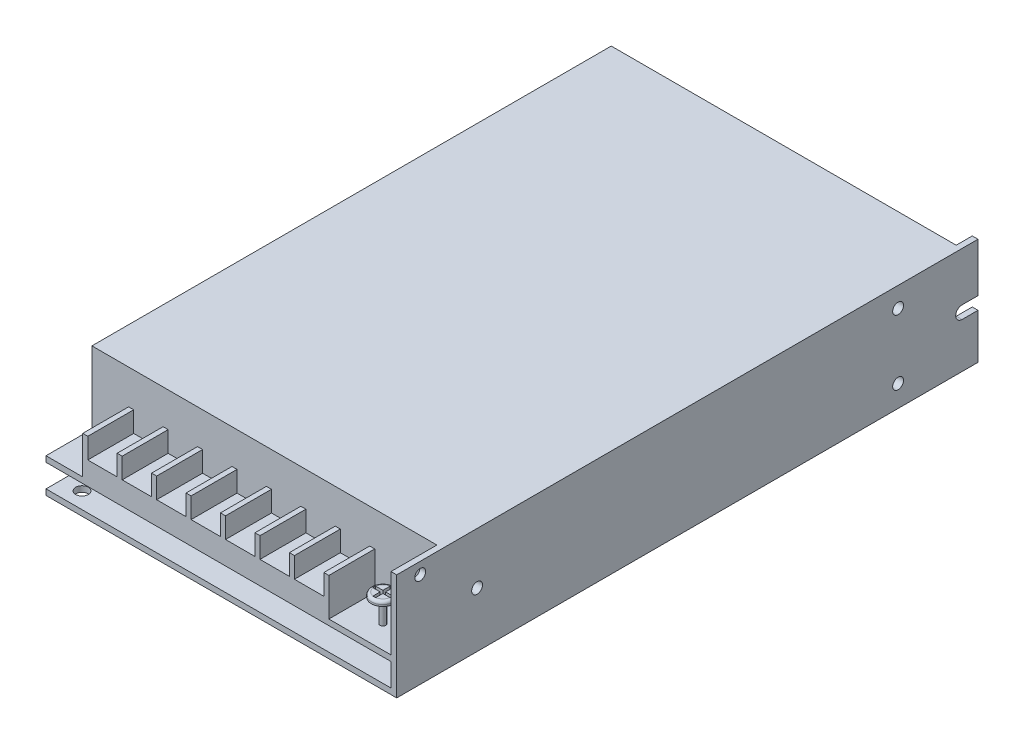
SolidWorks part; units mm, degrees
ref_plane "Front (1)" through (0, 0, 0) normal (0, 0, 1) x (1, 0, 0)
ref_plane "Top (2)" through (0, 0, 0) normal (0, 1, 0) x (1, 0, 0)
ref_plane "Right (3)" through (0, 0, 0) normal (1, 0, 0) x (0, 0, -1)
ref_axis "X-Axis" through (-80.9, 0, 0) along (1, 0, 0)
ref_axis "Y-Axis" through (0, -50, 0) along (0, 1, 0)
ref_axis "Z-Axis" through (0, 0, 50) along (0, 0, -1)
sketch "Sketch1" plane through (0, 0, 0) normal (0, 0, 1) x (1, 0, 0)
  line L1 (0, 0) -> (97, 0)
  line L2 (0, 0) -> (0, 29.492)
  line L3 (0, 29.492) -> (97, 29.492)
  line L4 (97, 0) -> (97, 29.492)
  dimension "D1" = 97
  dimension "D2" = 29.492
extrude "Boss-Extrude1" add sketch "Sketch1" against normal blind 160.778
sketch "Sketch2" plane through (0, 0, 0) normal (0, 0, 1) x (1, 0, 0)
  line L0 (95.4125, 29.492) -> (95.4125, 9.525)
  line L1 (97, 29.492) -> (0, 29.492) construction
  line L2 (95.4125, 9.525) -> (89.9973, 9.525)
  line L3 (59.182, 19.967) -> (59.182, 14.2875)
  line L4 (59.182, 14.2875) -> (67.31, 14.2875)
  line L5 (67.31, 14.2875) -> (67.31, 19.967)
  line L6 (67.31, 19.967) -> (68.707, 19.967)
  line L7 (89.9973, 9.525) -> (89.9973, 17.145)
  line L8 (89.9973, 17.145) -> (83.6472, 17.145)
  line L9 (83.6472, 17.145) -> (83.6472, 9.525)
  line L10 (83.6472, 9.525) -> (78.232, 9.525)
  line L11 (68.707, 19.967) -> (68.707, 14.2875)
  line L12 (59.182, 19.967) -> (57.785, 19.967)
  line L13 (57.785, 19.967) -> (57.785, 14.2875)
  line L14 (57.785, 14.2875) -> (49.657, 14.2875)
  line L15 (49.657, 14.2875) -> (49.657, 19.967)
  line L16 (49.657, 19.967) -> (48.26, 19.967)
  line L17 (48.26, 19.967) -> (48.26, 14.2875)
  line L18 (48.26, 14.2875) -> (40.132, 14.2875)
  line L19 (40.132, 14.2875) -> (40.132, 19.967)
  line L20 (40.132, 19.967) -> (38.735, 19.967)
  line L21 (38.735, 19.967) -> (38.735, 14.2875)
  line L22 (38.735, 14.2875) -> (30.607, 14.2875)
  line L23 (30.607, 14.2875) -> (30.607, 19.967)
  line L24 (30.607, 19.967) -> (29.21, 19.967)
  line L25 (29.21, 19.967) -> (29.21, 14.2875)
  line L26 (29.21, 14.2875) -> (21.082, 14.2875)
  line L27 (21.082, 14.2875) -> (21.082, 19.967)
  line L28 (21.082, 19.967) -> (19.685, 19.967)
  line L29 (19.685, 19.967) -> (19.685, 14.2875)
  line L30 (19.685, 14.2875) -> (11.557, 14.2875)
  line L31 (11.557, 14.2875) -> (11.557, 19.967)
  line L32 (11.557, 19.967) -> (10.16, 19.967)
  line L33 (10.16, 19.967) -> (10.16, 9.525)
  line L34 (10.16, 9.525) -> (0, 9.525)
  line L35 (0, 29.492) -> (0, 0) construction
  line L36 (0, 9.525) -> (0, 29.492)
  line L37 (0, 29.492) -> (95.4125, 29.492)
  line L38 (95.4125, 7.9375) -> (0, 7.9375)
  line L39 (0, 7.9375) -> (0, 1.5875)
  line L40 (0, 1.5875) -> (95.4125, 1.5875)
  line L41 (95.4125, 1.5875) -> (95.4125, 7.9375)
  line L42 (0, 1.5875) -> (0, 0)
  line L43 (0, 0) -> (97, 0)
  line L44 (97, 0) -> (97, 29.492)
  line L45 (97, 29.492) -> (95.4125, 29.492)
  line L46 (95.4125, 9.525) -> (95.4125, 7.9375)
  line L47 (68.707, 14.2875) -> (76.835, 14.2875)
  line L48 (76.835, 14.2875) -> (76.835, 19.967)
  line L49 (76.835, 19.967) -> (78.232, 19.967)
  line L50 (78.232, 19.967) -> (78.232, 9.525)
  line M29 (0, 29.492) -> (0, 0)
  line M32 (97, 29.492) -> (0, 29.492)
  dimension "D1" = 1.5875
  dimension "D2" = 1.5875
  dimension "D3" = 1.5875
  dimension "D4" = 6.35
  dimension "D5" = 7.62
  dimension "D8" = 6.35
  dimension "D10" = 8.128
  dimension "D11" = 1.397
  dimension "D12" = 10.16
  dimension "D13" = 9.525
  dimension "D14" = 6.35
extrude "Cut-Extrude1" cut sketch "Sketch2" against normal blind 12.7 contours L34 L33 L32 L31 L30 L29 L28 L27 L26 L25 L24 L23 L22 L21 L20 L19 L18 L17 L16 L15 L14 L13 L12 L10 L9 L8 L7 L5 L2 L0 M32 M29 | L40 L41 L38 M29 region at (47.3442, 21.4924, 0) region at (47.7063, 4.7625, 0)
sketch "Sketch3" plane through (0, 29.492, 0) normal (0, 1, 0) x (1, 0, 0)
  line L1 (83.6472, 12.7) -> (89.9973, 12.7)
  line L2 (83.6472, 12.7) -> (83.6472, 0)
  line L3 (83.6472, 0) -> (89.9973, 0)
  line L4 (89.9973, 12.7) -> (89.9973, 0)
  line L10 (86.8223, 6.35) -> (83.6472, 6.35) construction
  circle A1 centre (86.8223, 6.35) radius 3.175
  line M4 (0, 12.7) -> (95.4125, 12.7)
extrude "Cut-Extrude2" cut sketch "Sketch3" against normal up to surface (19.967 mm away) contours A1 L2 L3 L4 | A1 L4 L2 M4 region at (86.8222, 29.492, -10.7067) region at (86.8222, 29.492, -1.9933) up to face at (80.9396, 9.525, -6.35)
sketch "Sketch4" plane through (0, 9.525, 0) normal (0, 1, 0) x (1, 0, 0)
  circle A2 centre (86.8223, 6.35) radius 0.7937
  circle A3 centre (86.8223, 6.35) radius 3.175
  circle A6 centre (86.8223, 6.35) radius 3.175 construction
  dimension "D1" = 1.5875
extrude "Cut-Extrude3" cut sketch "Sketch4" along normal blind 6.35
fillet "Fillet1" radius 0.7937 1 edges at (86.8223, 17.145, -3.175)
sketch "Sketch5" plane through (0, 17.145, 0) normal (0, 1, 0) x (1, 0, 0)
  line L0 (86.4413, 8.7313) -> (86.4413, 6.731)
  line L1 (86.4413, 6.731) -> (84.441, 6.731)
  line L2 (84.441, 6.731) -> (84.441, 5.969)
  line L3 (84.441, 5.969) -> (86.4413, 5.969)
  line L4 (86.4413, 5.969) -> (86.4413, 3.9688)
  line L5 (86.4413, 3.9688) -> (87.2033, 3.9688)
  line L6 (87.2033, 3.9688) -> (87.2033, 5.969)
  line L7 (87.2033, 5.969) -> (89.2035, 5.969)
  line L8 (89.2035, 5.969) -> (89.2035, 6.731)
  line L9 (89.2035, 6.731) -> (87.2033, 6.731)
  line L10 (87.2033, 6.731) -> (87.2033, 8.7313)
  line L11 (87.2033, 8.7313) -> (86.4413, 8.7313)
  line L12 (86.4413, 6.731) -> (87.2033, 5.969) construction
  circle A1 centre (86.8223, 6.35) radius 2.3812 construction
  point P4 (86.8223, 6.35)
  dimension "D1" = 4.7625
  dimension "D2" = 0.762
extrude "Cut-Extrude4" cut sketch "Sketch5" against normal blind 1.27
sketch "Sketch6" plane through (0, 0, -160.778) normal (0, 0, -1) x (-1, 0, 0)
  line L0 (0, 0) -> (-97, 0) construction
  line L1 (-85.2525, 1.5875) -> (-95.4125, 1.5875)
  line L2 (-85.2525, 1.5875) -> (-85.2525, 29.492)
  line L3 (-85.2525, 29.492) -> (-95.4125, 29.492)
  line L4 (-95.4125, 1.5875) -> (-95.4125, 29.492)
  line L9 (-97, 0) -> (-97, 29.492) construction
  line L10 (-97, 29.492) -> (0, 29.492) construction
  dimension "D1" = 1.5875
  dimension "D2" = 1.5875
  dimension "D3" = 10.16
extrude "Cut-Extrude6" cut sketch "Sketch6" against normal blind 4.445
sketch "Sketch7" plane through (97, 0, 0) normal (1, 0, 0) x (0, 0, -1)
  line L0 (160.778, 15.974) -> (156.3624, 15.974)
  line L1 (160.778, 0) -> (160.778, 29.492) construction
  line L3 (156.3624, 12.474) -> (160.778, 12.474)
  line L4 (160.778, 15.974) -> (160.778, 12.474)
  line L5 (160.778, 0) -> (0, 0) construction
  line L6 (160.778, 0) -> (0, 0) construction
  line L7 (0, 0) -> (0, 29.492) construction
  circle A0 centre (6.5024, 26.289) radius 1.5
  circle A1 centre (22.225, 15.24) radius 1.5
  circle A2 centre (138.684, 6) radius 1.5
  arc A3 (156.3624, 15.974) -> (156.3624, 12.474) centre (156.3624, 14.224) ccw
  circle A4 centre (138.684, 23.9832) radius 1.5
  dimension "D1" = 3
  dimension "D2" = 26.289
  dimension "D3" = 6.5024
  dimension "D4" = 15.24
  dimension "D5" = 22.225
  dimension "D6" = 138.684
  dimension "D7" = 3.5
  dimension "D8" = 14.224
  dimension "D9" = 149.86
  dimension "D10" = 17.9832
  dimension "D11" = 6
extrude "Cut-Extrude7" cut sketch "Sketch7" against normal blind 6.35
sketch "Sketch8" plane through (0, 0, 0) normal (0, -1, 0) x (1, 0, 0)
  line L0 (95.4125, 0) -> (0, 0) construction
  line L1 (0, -160.778) -> (0, 0) construction
  line L3 (92.146, -160.778) -> (92.146, -157.988)
  line L4 (0, -160.778) -> (97, -160.778) construction
  line L5 (0, 0) -> (97, 0) construction
  line L6 (88.646, -157.988) -> (88.646, -160.778)
  line L7 (88.646, -160.778) -> (92.146, -160.778)
  line L8 (97, -160.778) -> (97, 0) construction
  circle A0 centre (65.25, -24.003) radius 1
  circle A1 centre (65.25, -102.87) radius 1
  arc A2 (92.146, -157.988) -> (88.646, -157.988) centre (90.396, -157.988) ccw
  circle A3 centre (5.461, -4.4958) radius 1.75
  dimension "D4" = 2
  dimension "D8" = 3.5
  dimension "D2" = 24.003
  dimension "D3" = 31.75
  dimension "D5" = 3.5
  dimension "D6" = 102.87
  dimension "D7" = 6.604
  dimension "D9" = 4.4958
  dimension "D10" = 5.461
  dimension "D11" = 55.118
extrude "Cut-Extrude8" cut sketch "Sketch8" against normal blind 6.35
sketch "Sketch9" plane through (0, 0, 0) normal (-1, 0, 0) x (0, 0, 1)
  line L0 (-160.778, 7.874) -> (-156.333, 12.319)
  line L1 (-160.778, 29.492) -> (-160.778, 0) construction
  line L2 (-156.333, 12.319) -> (-156.333, 29.492)
  line L3 (-160.778, 29.492) -> (-12.7, 29.492) construction
  line L4 (-156.333, 29.492) -> (-160.778, 29.492)
  line L5 (-160.778, 29.492) -> (-160.778, 7.874)
  line L6 (-160.778, 0) -> (0, 0) construction
  dimension "D1" = 4.445
  dimension "D2" = 45
  dimension "D3" = 7.874
extrude "Cut-Extrude9" cut sketch "Sketch9" against normal up to surface (95.4125 mm away) up to face at (95.4125, 8.1194, -158.1169)
